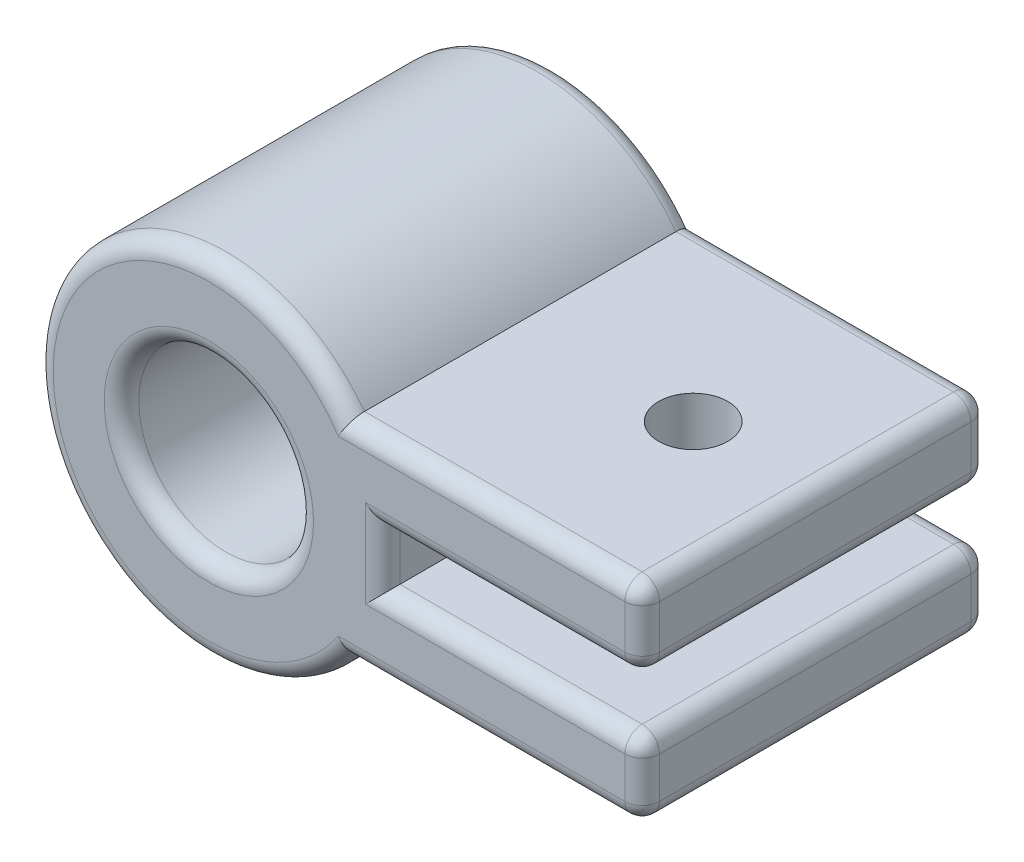
SolidWorks part; units mm, degrees
material "黄铜"
ref_plane "前视基准面" through (0, 0, 0) normal (0, 0, 1) x (1, 0, 0)
ref_plane "上视基准面" through (0, 0, 0) normal (0, 1, 0) x (1, 0, 0)
ref_plane "右视基准面" through (0, 0, 0) normal (1, 0, 0) x (0, 0, -1)
sketch "草图1" plane through (0, 0, 0) normal (0, 0, 1) x (1, 0, 0)
  circle A0 centre (0, 0) radius 10
  circle A1 centre (0, 0) radius 5.05
  dimension "D1" = 10.1
  dimension "D2" = 20
extrude "凸台-拉伸1" add sketch "草图1" along normal blind 20
sketch "草图2" plane through (0, 0, 0) normal (0, 1, 0) x (1, 0, 0)
  line L1 (5.05, 0) -> (25.05, 0)
  line L2 (5.05, 0) -> (5.05, -20)
  line L3 (5.05, -20) -> (25.05, -20)
  line L4 (25.05, 0) -> (25.05, -20)
  circle A0 centre (18, -10) radius 2
  point P8 (25.05, -10)
  dimension "D3" = 4
  dimension "D4" = 18
  dimension "D1" = 20
  dimension "D2" = 0
  dimension "D5" = 20
extrude "凸台-拉伸2" add sketch "草图2" along normal blind 6 and the other way blind 6
sketch "草图3" plane through (25.05, 0, 0) normal (1, 0, 0) x (0, 0, -1)
  line L0 (-20, -6) -> (-20, 6) construction
  line L1 (-20, 1.4729) -> (0, 1.4729)
  line L2 (-20, 1.4729) -> (-20, -1.6271)
  line L3 (-20, -1.6271) -> (0, -1.6271)
  line L4 (0, 1.4729) -> (0, -1.6271)
  line L5 (0, -6) -> (0, 6) construction
  dimension "D1" = 3.1
extrude "切除-拉伸1" cut sketch "草图3" against normal blind 15
fillet "圆角1" radius 1 22 edges at (25.05, -6, 10) (25.05, -1.6271, 10) (25.05, 6, 10) (25.05, 1.4729, 10) (5.05, 0, 0) (16.525, 6, 0) (-10, 0, 0) (16.525, -6, 0) (25.05, -3.8136, 0) (17.55, -1.6271, 0) (10.05, -0.0771, 0) (17.55, 1.4729, 0) (25.05, 3.7364, 0) (5.05, 0, 20) (10.05, -0.0771, 20) (17.55, -1.6271, 20) (25.05, -3.8136, 20) (16.525, -6, 20) (-10, 0, 20) (16.525, 6, 20) (25.05, 3.7364, 20) (17.55, 1.4729, 20)
